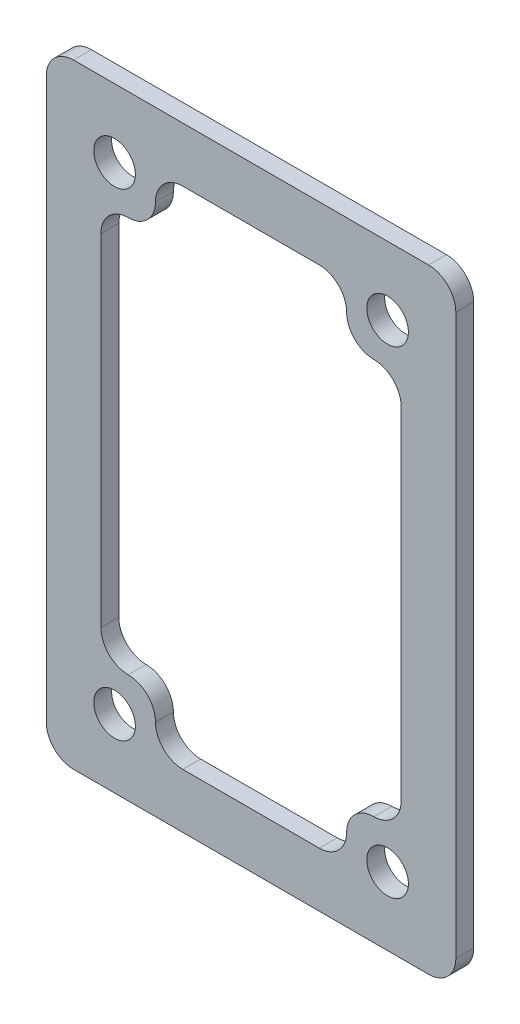
SolidWorks part; units mm, degrees
material "ABS"
ref_plane "前视基准面" through (0, 0, 0) normal (0, 0, 1) x (1, 0, 0)
ref_plane "上视基准面" through (0, 0, 0) normal (0, 1, 0) x (1, 0, 0)
ref_plane "右视基准面" through (0, 0, 0) normal (1, 0, 0) x (0, 0, -1)
sketch "草图1" plane through (0, 0, 0) normal (0, 0, 1) x (1, 0, 0)
  line L1 (-15, -22.5) -> (15, -22.5)
  line L2 (-15, -22.5) -> (-15, 22.5)
  line L3 (-15, 22.5) -> (15, 22.5)
  line L4 (15, -22.5) -> (15, 22.5)
  line L5 (0, 22.5) -> (0, -22.5) construction
  line L6 (-15, 0) -> (15, 0) construction
  point P0 (0, 0)
  dimension "D1" = 45
  dimension "D2" = 30
extrude "凸台-拉伸1" add sketch "草图1" along normal blind 1.31
sketch "草图2" plane through (0, 0, 1.31) normal (0, 0, 1) x (1, 0, 0)
  line L0 (15, -22.5) -> (15, 22.5) construction
  line L1 (-10, -17.5) -> (10, -17.5) construction
  line L2 (-10, -17.5) -> (-10, 17.5) construction
  line L3 (-10, 17.5) -> (10, 17.5) construction
  line L4 (10, -17.5) -> (10, 17.5) construction
  line L5 (0, 17.5) -> (0, -17.5) construction
  line L6 (-10, 0) -> (10, 0) construction
  line L7 (15, 22.5) -> (-15, 22.5) construction
  circle A0 centre (-10, 17.5) radius 1.525
  circle A1 centre (10, 17.5) radius 1.525
  circle A2 centre (-10, -17.5) radius 1.525
  circle A3 centre (10, -17.5) radius 1.525
  point P0 (0, 0)
  dimension "D3" = 3.05
  dimension "D1" = 5
  dimension "D2" = 5
extrude "切除-拉伸1" cut sketch "草图2" against normal blind 10
sketch "草图3" plane through (0, 0, 1.31) normal (0, 0, 1) x (1, 0, 0)
  line L0 (15, 22.5) -> (-15, 22.5) construction
  line L1 (-7, -18.5) -> (7, -18.5)
  line L2 (-7, -18.5) -> (-7, 18.5)
  line L3 (-7, 18.5) -> (7, 18.5)
  line L4 (7, -18.5) -> (7, 18.5)
  line L5 (0, 18.5) -> (0, -18.5) construction
  line L6 (-7, 0) -> (7, 0) construction
  circle A0 centre (10, 17.5) radius 1.525 construction
  point P0 (0, 0)
  dimension "D1" = 4
  dimension "D2" = 3
extrude "切除-拉伸2" cut sketch "草图3" against normal blind 10
sketch "草图4" plane through (0, 0, 1.31) normal (0, 0, 1) x (1, 0, 0)
  line L0 (15, -22.5) -> (15, 22.5) construction
  line L1 (-11, -14.5) -> (11, -14.5)
  line L2 (-11, -14.5) -> (-11, 14.5)
  line L3 (-11, 14.5) -> (11, 14.5)
  line L4 (11, -14.5) -> (11, 14.5)
  line L5 (0, 14.5) -> (0, -14.5) construction
  line L6 (-11, 0) -> (11, 0) construction
  circle A0 centre (10, 17.5) radius 1.525 construction
  point P0 (0, 0)
  dimension "D1" = 4
  dimension "D2" = 3
extrude "切除-拉伸3" cut sketch "草图4" against normal blind 10
fillet "圆角1" radius 2 12 edges at (-7, -18.5, 0.655) (11, -14.5, 0.655) (11, 14.5, 0.655) (7, 14.5, 0.655) (7, 18.5, 0.655) (-7, 18.5, 0.655) (-7, 14.5, 0.655) (-11, 14.5, 0.655) (-11, -14.5, 0.655) (-7, -14.5, 0.655) (7, -14.5, 0.655) (7, -18.5, 0.655)
fillet "圆角2" radius 2 4 edges at (15, -22.5, 0.655) (-15, -22.5, 0.655) (-15, 22.5, 0.655) (15, 22.5, 0.655)
sketch "草图5" [suppressed] plane through (0, 0, 5) normal (0, 0, 1) x (1, 0, 0)
  line L0 (0, -6.35) -> (0, 6.35) construction
  circle A0 centre (0, -6.35) radius 1.2
  circle A1 centre (0, 6.35) radius 1.2
  point P4 (0, 0)
  dimension "D2" = 2.4
  dimension "D1" = 12.7
extrude "切除-拉伸4" [suppressed] cut sketch "草图5" against normal blind 10
